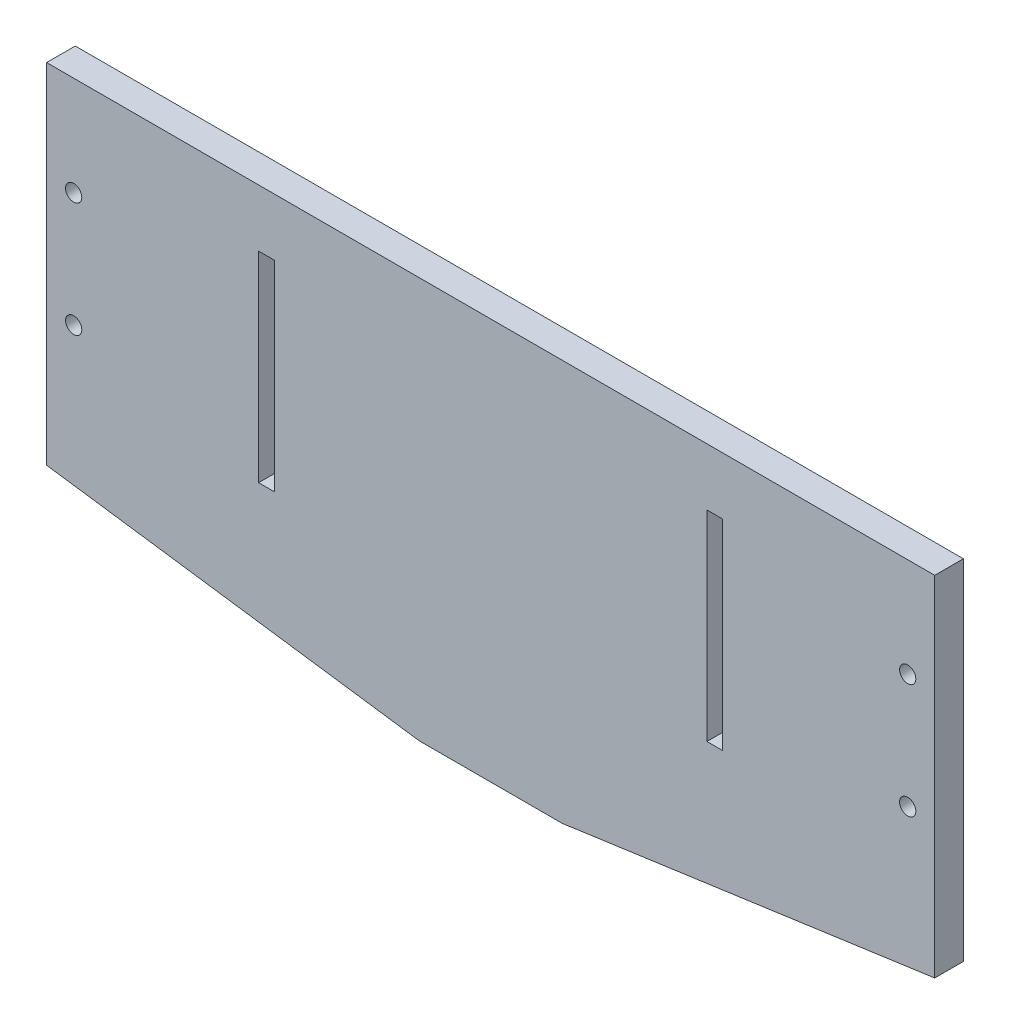
SolidWorks part; units mm, degrees
material "Acrylic (Medium-high impact)"
ref_plane "Front Plane" through (0, 0, 0) normal (0, 0, 1) x (1, 0, 0)
ref_plane "Top Plane" through (0, 0, 0) normal (0, 1, 0) x (1, 0, 0)
ref_plane "Right Plane" through (0, 0, 0) normal (1, 0, 0) x (0, 0, -1)
sketch "Sketch1" plane through (0, 0, 0) normal (0, 0, 1) x (1, 0, 0)
  line L1 (196.85, 127) -> (0, 127)
  line L2 (196.85, 127) -> (196.85, 0)
  line L3 (196.85, 0) -> (0, 0)
  line L4 (0, 127) -> (0, 0)
  line L5 (196.85, 127) -> (0, 0) construction
  line L6 (196.85, 0) -> (0, 127) construction
  point P0 (98.425, 63.5)
  dimension "D1" = 127
  dimension "D2" = 196.85
extrude "Boss-Extrude1" add sketch "Sketch1" along normal blind 6.35
hole_wizard "M3 Clearance Hole1" positions "Sketch2" profile "Sketch3" hole size "M3" standard "ANSI Metric" end condition through all
sketch "Sketch2" plane through (0, 0, 6.35) normal (0, 0, 1) x (1, 0, 0)
  line L0 (0, 127) -> (0, 0) construction
  line L1 (196.85, 127) -> (0, 127) construction
  line L2 (196.85, 0) -> (196.85, 127) construction
  point P0 (5.9944, 105.0036)
  point P2 (5.9944, 79.6036)
  point P4 (190.8556, 79.6036)
  point P6 (190.8556, 105.0036)
  dimension "D1" = 5.9944
  dimension "D2" = 21.9964
  dimension "D3" = 5.9944
  dimension "D4" = 25.4
sketch "Sketch3" plane through (5.9944, 105.0036, 6.35) normal (1, 0, 0) x (0, -1, 0)
  line L0 (0, 0) -> (0, 6.35)
  line L1 (0, 6.35) -> (1.8, 6.35)
  line L2 (1.8, 6.35) -> (1.8, 0)
  line L5 (1.8, 0) -> (0, 0)
  line L11 (0, -6.35) -> (0, 107.95) construction
  dimension "Thru Hole Dia." = 3.6
  dimension "Thru Hole Depth" = 6.35
sketch "Sketch4" plane through (0, 0, 6.35) normal (0, 0, 1) x (1, 0, 0)
  line L0 (0, 127) -> (0, 0) construction
  line L1 (46.99, 114.3) -> (50.4952, 114.3)
  line L2 (46.99, 114.3) -> (46.99, 69.85)
  line L3 (46.99, 69.85) -> (50.4952, 69.85)
  line L4 (50.4952, 114.3) -> (50.4952, 69.85)
  line L5 (146.3548, 114.3) -> (149.86, 114.3)
  line L6 (146.3548, 114.3) -> (146.3548, 69.85)
  line L7 (146.3548, 69.85) -> (149.86, 69.85)
  line L8 (149.86, 114.3) -> (149.86, 69.85)
  line L9 (196.85, 0) -> (196.85, 127) construction
  line L10 (196.85, 127) -> (0, 127) construction
  dimension "D1" = 3.5052
  dimension "D2" = 44.45
  dimension "D3" = 46.99
  dimension "D4" = 46.99
  dimension "D5" = 12.7
extrude "Cut-Extrude1" cut sketch "Sketch4" against normal through all
sketch "Sketch5" plane through (0, 0, 6.35) normal (0, 0, 1) x (1, 0, 0)
  line L0 (0, 49.7016) -> (82.55, 38.1)
  line L1 (0, 127) -> (0, 0) construction
  line L2 (82.55, 38.1) -> (114.3, 38.1)
  line L3 (114.3, 38.1) -> (196.85, 49.7016)
  line L4 (196.85, 0) -> (196.85, 127) construction
  line L5 (196.85, 49.7016) -> (196.85, 0)
  line L6 (196.85, 0) -> (0, 0)
  line L7 (0, 0) -> (0, 49.7016)
  dimension "D1" = 8
  dimension "D2" = 8
  dimension "D3" = 31.75
  dimension "D5" = 38.1
extrude "Cut-Extrude2" cut sketch "Sketch5" against normal through all
